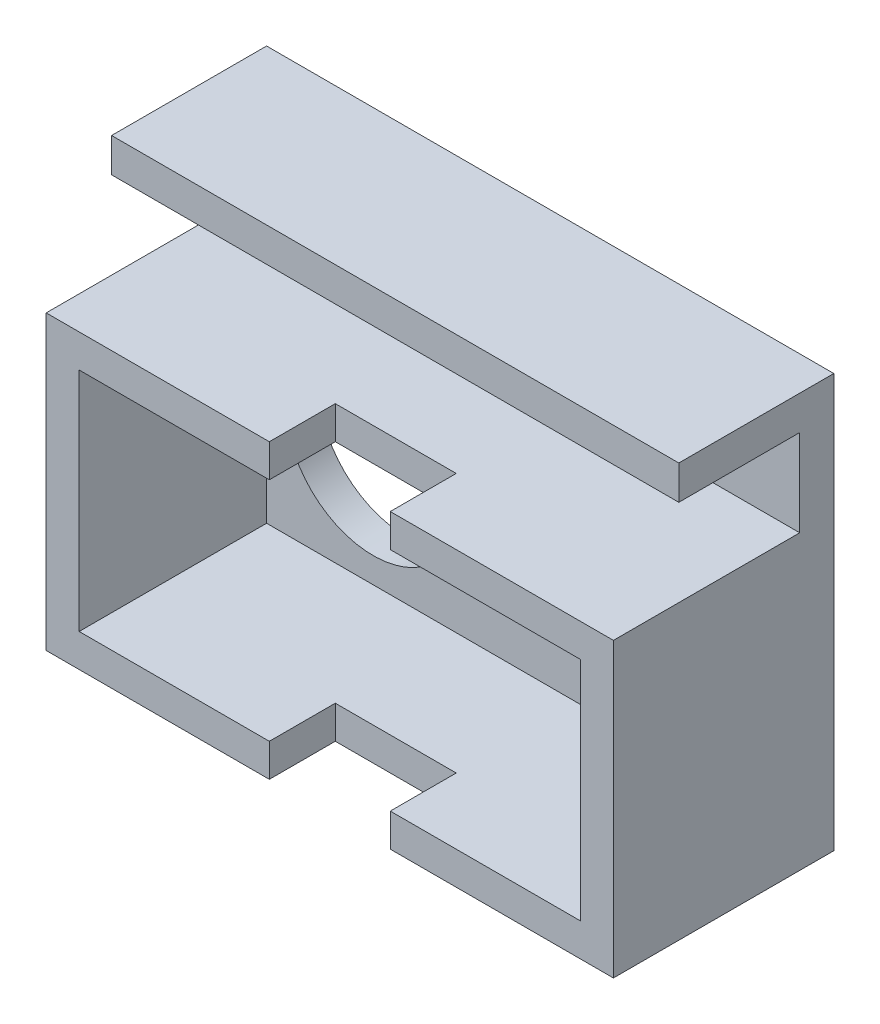
SolidWorks part; units mm, degrees
ref_plane "Front Plane" through (0, 0, 0) normal (0, 0, 1) x (1, 0, 0)
ref_plane "Top Plane" through (0, 0, 0) normal (0, 1, 0) x (1, 0, 0)
ref_plane "Right Plane" through (0, 0, 0) normal (1, 0, 0) x (0, 0, -1)
sketch "Sketch1" plane through (0, 0, 0) normal (0, 0, 1) x (1, 0, 0)
  line L1 (0, 0) -> (51.6, 0)
  line L2 (0, 0) -> (0, 26.6)
  line L3 (0, 26.6) -> (51.6, 26.6)
  line L4 (51.6, 0) -> (51.6, 26.6)
extrude "Boss-Extrude1" add sketch "Sketch1" along normal blind 23.05
sketch "Sketch2" plane through (0, 0, 23.05) normal (0, 0, 1) x (1, 0, 0)
  line L0 (0, 26.6) -> (3, 26.6)
  line L1 (51.6, 26.6) -> (0, 26.6) construction
  line L2 (3, 26.6) -> (3, 23.6)
  line L3 (51.6, 0) -> (48.6, 0)
  line L4 (0, 0) -> (51.6, 0) construction
  line L5 (48.6, 0) -> (48.6, 3)
  line L6 (25.8, 23.6) -> (25.8, 26.6)
  line L7 (3, 23.6) -> (48.6, 23.6)
  line L8 (3, 23.6) -> (3, 3)
  line L9 (3, 3) -> (48.6, 3)
  line L10 (48.6, 23.6) -> (48.6, 3)
  line L11 (25.8, 26.6) -> (31.3, 26.6)
  line L12 (25.8, 3) -> (25.8, 0)
  line L13 (25.8, 0) -> (20.3, 0)
  line L15 (20.3, 0) -> (31.3, 0)
  line L16 (20.3, 0) -> (20.3, 26.6)
  line L17 (20.3, 26.6) -> (31.3, 26.6)
  line L18 (31.3, 0) -> (31.3, 26.6)
extrude "Cut-Extrude1" cut sketch "Sketch2" against normal blind 4 contours L9 L16 L7 L8 | L9 L18 L7 L16 | L18 L9 L10 L7 | L16 L7 L6 | L7 L18 L6 | L16 L4 L12 L9 | L4 L18 L9 L12 region at (23.05, 1.5, 23.05) region at (28.55, 1.5, 23.05) region at (25.8, 13.3, 23.05) region at (11.65, 13.3, 23.05) region at (23.05, 25.1, 23.05) region at (39.95, 13.3, 23.05) region at (28.55, 25.1, 23.05)
sketch "Sketch3" plane through (0, 0, 19.05) normal (0, 0, 1) x (1, 0, 0)
  line L1 (3, 23.6) -> (48.6, 23.6)
  line L2 (3, 23.6) -> (3, 3)
  line L3 (3, 3) -> (48.6, 3)
  line L4 (48.6, 23.6) -> (48.6, 3)
extrude "Cut-Extrude2" cut sketch "Sketch3" against normal blind 16.05
sketch "Sketch4" plane through (0, 0, 0) normal (0, 0, -1) x (-1, 0, 0)
  line L0 (-3.1, 23.5) -> (-3.1, 13.3)
  line L1 (-51.6, 26.6) -> (-48.5, 26.6)
  line L2 (-51.6, 26.6) -> (-51.6, 23.5)
  line L3 (-51.6, 23.5) -> (-48.5, 23.5)
  line L4 (-48.5, 26.6) -> (-48.5, 23.5)
  line L5 (-48.5, 23.5) -> (-38.9, 23.5)
  line L6 (-48.5, 23.5) -> (-48.5, 13.3)
  line L7 (-48.5, 13.3) -> (-38.9, 13.3)
  line L8 (-38.9, 23.5) -> (-38.9, 13.3)
  line L9 (0, 26.6) -> (-3.1, 26.6)
  line L10 (0, 26.6) -> (0, 23.5)
  line L11 (0, 23.5) -> (-3.1, 23.5)
  line L12 (-3.1, 26.6) -> (-3.1, 23.5)
  line L13 (-3.1, 13.3) -> (-12.7, 13.3)
  line L15 (-12.7, 13.3) -> (-3.1, 13.3)
  line L16 (-12.7, 13.3) -> (-12.7, 23.5)
  line L17 (-12.7, 23.5) -> (-3.1, 23.5)
  line L18 (-3.1, 13.3) -> (-3.1, 23.5)
  circle A0 centre (-38.9, 13.3) radius 8
  circle A1 centre (-12.7, 13.3) radius 8
extrude "Cut-Extrude3" cut sketch "Sketch4" against normal blind 3.1 contours L7 A0 L8 | L8 A0 L7 | L15 A1 L16 | L16 A1 L15 region at (13.8318, 12.1682, 0) region at (9.3047, 16.6953, 0) region at (37.7682, 12.1682, 0) region at (42.2953, 16.6953, 0)
sketch "Sketch6" plane through (0, 26.6, 0) normal (0, 1, 0) x (1, 0, 0)
  line L0 (51.6, -23.05) -> (51.6, 0) construction
  line L1 (0, 0) -> (51.6, 0)
  line L2 (0, 0) -> (0, -3.1)
  line L3 (0, -3.1) -> (51.6, -3.1)
  line L4 (51.6, 0) -> (51.6, -3.1)
extrude "Boss-Extrude2" add sketch "Sketch6" along normal blind 11
sketch "Sketch7" plane through (0, 0, 3.1) normal (0, 0, 1) x (1, 0, 0)
  line L0 (51.6, 37.6) -> (51.6, 26.6) construction
  line L1 (0, 37.6) -> (51.6, 37.6)
  line L2 (0, 37.6) -> (0, 34.5)
  line L3 (0, 34.5) -> (51.6, 34.5)
  line L4 (51.6, 37.6) -> (51.6, 34.5)
extrude "Boss-Extrude3" add sketch "Sketch7" along normal blind 11
sketch "Sketch8" plane through (0, 0, 19.05) normal (0, 0, 1) x (1, 0, 0)
  line L1 (31.3, 0) -> (20.3, 0)
  line L2 (31.3, 0) -> (31.3, 26.6)
  line L3 (31.3, 26.6) -> (20.3, 26.6)
  line L4 (20.3, 0) -> (20.3, 26.6)
extrude "Cut-Extrude4" cut sketch "Sketch8" against normal blind 5
sketch "Sketch9" plane through (0, 0, 23.05) normal (0, 0, 1) x (1, 0, 0)
  line L1 (0, 0) -> (51.6, 0)
  line L2 (0, 0) -> (0, 26.6)
  line L3 (0, 26.6) -> (51.6, 26.6)
  line L4 (51.6, 0) -> (51.6, 26.6)
extrude "Cut-Extrude5" cut sketch "Sketch9" against normal blind 5
sketch "Sketch10" plane through (0, 0, 18.05) normal (0, 0, 1) x (1, 0, 0)
  line L1 (20.3, 0) -> (0, 0)
  line L2 (20.3, 0) -> (20.3, 26.6)
  line L3 (20.3, 26.6) -> (0, 26.6)
  line L4 (0, 0) -> (0, 26.6)
  line L5 (20.3, 3) -> (3, 3)
  line L6 (20.3, 3) -> (20.3, 23.6)
  line L7 (20.3, 23.6) -> (3, 23.6)
  line L8 (3, 3) -> (3, 23.6)
  line L9 (51.6, 0) -> (31.3, 0)
  line L10 (51.6, 0) -> (51.6, 26.6)
  line L11 (51.6, 26.6) -> (31.3, 26.6)
  line L12 (31.3, 0) -> (31.3, 26.6)
  line L13 (48.6, 3) -> (31.3, 3)
  line L14 (48.6, 3) -> (48.6, 23.6)
  line L15 (48.6, 23.6) -> (31.3, 23.6)
  line L16 (31.3, 3) -> (31.3, 23.6)
  line M9 (20.3, 0) -> (20.3, 3)
  line M10 (20.3, 3) -> (3, 3)
  line M11 (3, 3) -> (3, 23.6)
  line M12 (3, 23.6) -> (20.3, 23.6)
  line M13 (20.3, 23.6) -> (20.3, 26.6)
  line M14 (20.3, 26.6) -> (0, 26.6)
  line M15 (0, 26.6) -> (0, 0)
  line M16 (0, 0) -> (20.3, 0)
extrude "Boss-Extrude4" add sketch "Sketch10" along normal blind 2 contours L15 L14 L13 L12 L9 L10 L11 | M16 M9 M10 M11 M12 M13 M14 M15 region at (10.15, 0.3346, 18.05) region at (41.45, 0.3346, 18.05)
